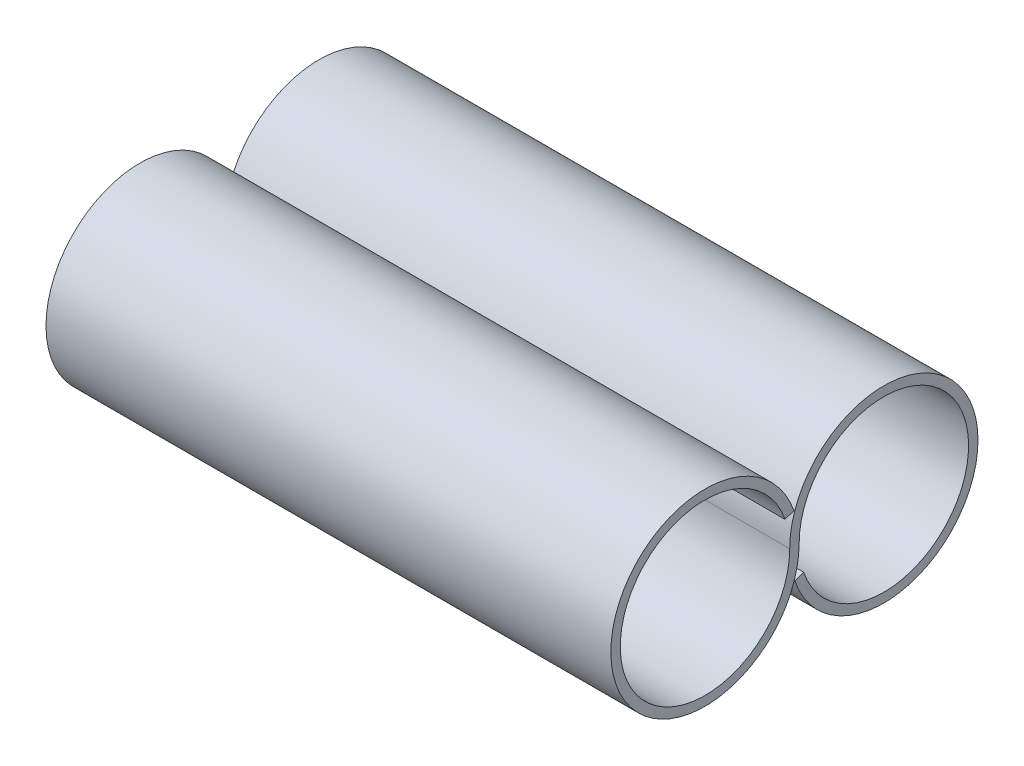
SolidWorks part; units mm, degrees
ref_plane "Front" through (0, 0, 0) normal (0, 0, 1) x (1, 0, 0)
ref_plane "Top" through (0, 0, 0) normal (0, 1, 0) x (1, 0, 0)
ref_plane "Right" through (0, 0, 0) normal (1, 0, 0) x (0, 0, -1)
sketch "Sketch2" plane through (0, 0, 0) normal (1, 0, 0) x (0, 0, -1)
  line L0 (0.7393, 3.6738) -> (-0.2053, 3.3456)
  line L1 (0.8231, -2.82) -> (1.7701, -2.4987)
  circle A0 centre (-8.7069, 0.3922) radius 9 construction
  circle A1 centre (10.2931, 0.3922) radius 9 construction
  circle A2 centre (-8.7069, 0.3922) radius 10 construction
  circle A3 centre (10.2931, 0.3922) radius 10 construction
  arc A4 (-0.2053, 3.3456) -> (0.2931, 0.3922) centre (-8.7069, 0.3922) ccw
  arc A5 (0.2931, 0.3922) -> (0.8231, -2.82) centre (10.2931, 0.3922) cw
  arc A6 (1.7701, -2.4987) -> (1.2931, 0.3922) centre (10.2931, 0.3922) ccw
  arc A7 (1.2931, 0.3922) -> (0.7393, 3.6738) centre (-8.7069, 0.3922) cw
  point P0 (0.7393, 3.6738)
  point P2 (0, 0)
  point P16 (0, 0)
  point P17 (0, 0)
  point P18 (0, 0)
  point P19 (0, 0)
  point P20 (0, 0)
  point P21 (0, 0)
  point P22 (0, 0)
  point P23 (0, 0)
  point P24 (0, 0)
  point P25 (0, 0)
  point P26 (0, 0)
  point P27 (0, 0)
  point P28 (0.6868, -2.7483)
  point P29 (0, 0)
  dimension "D1" = 18
  dimension "D2" = 18
  dimension "D4" = 20
  dimension "D5" = 20
  dimension "D3" = 19
extrude "Boss-Extrude2" add sketch "Sketch2" along normal blind 60
